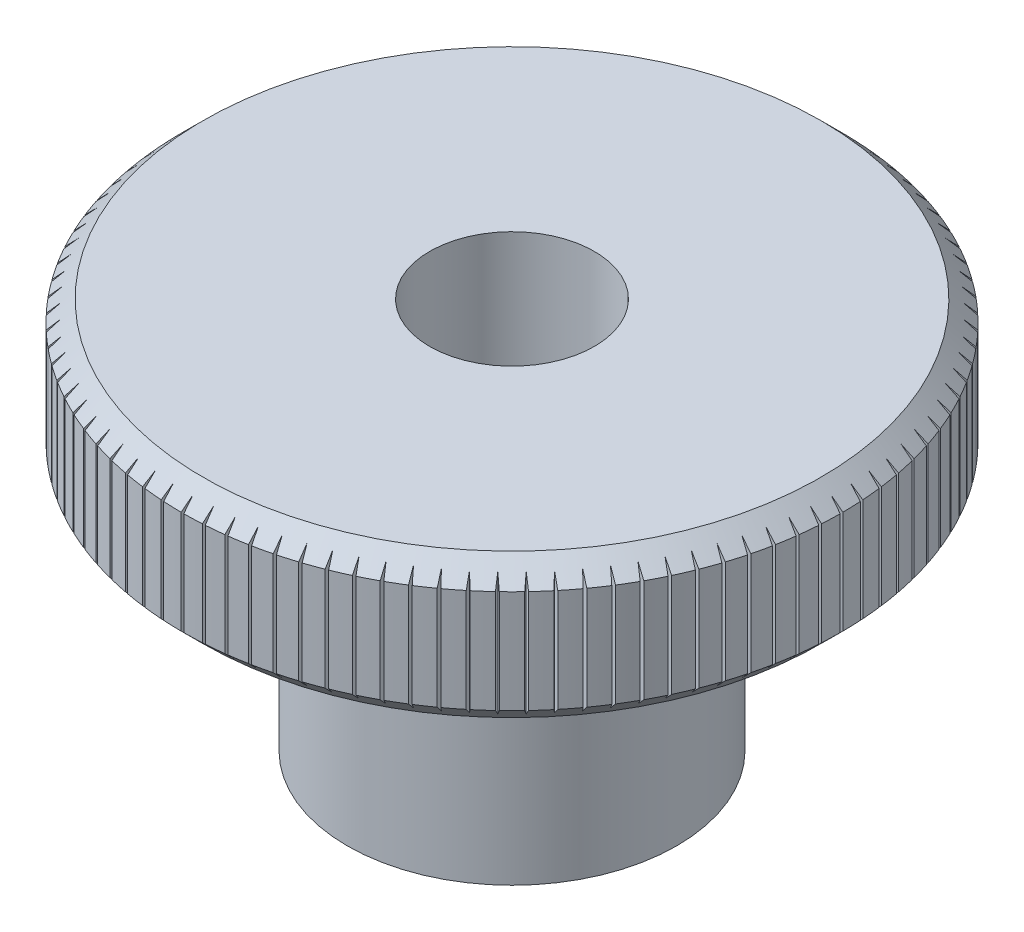
SolidWorks part; units mm, degrees
ref_plane "Front Plane" through (0, 0, 0) normal (0, 0, 1) x (1, 0, 0)
ref_plane "Top Plane" through (0, 0, 0) normal (0, 1, 0) x (1, 0, 0)
ref_plane "Right Plane" through (0, 0, 0) normal (1, 0, 0) x (0, 0, -1)
sketch "Sketch1" plane through (0, 0, 0) normal (0, 0, 1) x (1, 0, 0)
  line L0 (0, 0) -> (0, -3885.4477) construction
  line L1 (2, 0) -> (2, 9.5)
  line L2 (2, 9.5) -> (8, 9.5)
  line L3 (8, 9.5) -> (8, 6)
  line L4 (8, 6) -> (4, 6)
  line L5 (4, 6) -> (4, 0)
  line L6 (4, 0) -> (2, 0)
  dimension "INNER DIAM" = 4
  dimension "HEAD DIAM" = 16
  dimension "BOSS DIAM" = 8
  dimension "HEIGHT" = 9.5
  dimension "KNURLED HEIGHT" = 3.5
revolve "Revolve1" add sketch "Sketch1" angle 360 about L0
fillet "Fillet1" radius 0.8 1 edges at (0, 6, 4)
chamfer "Chamfer1" distance 0.5 angle 45 2 edges at (0, 6, 8) (0, 9.5, 8)
sketch "Sketch2" plane through (0, 9.5, 0) normal (0, 1, 0) x (1, 0, 0)
  line L0 (0.0329, 8) -> (-0.0329, 8)
  line L1 (-0.0329, 8) -> (0, 7.75)
  line L2 (0, 7.75) -> (0.0329, 8)
  circle A1 centre (0, 0) radius 8 construction
  point P0 (0, 8)
  point P3 (0, 8)
  dimension "D1" = 0.25
  dimension "D2" = 15
extrude "Cut-Extrude1" cut sketch "Sketch2" against normal through all
pattern_circular "CirPattern1" count 100 over 360 about axis through (0, 0, 0) along (0, 1, 0) of "Cut-Extrude1" reverse direction yes
equation "\"D1@Fillet1\"= \"INNER DIAM@Sketch1\" / 5"
equation "\"D1@Chamfer1\" = \"INNER DIAM@Sketch1\" / 8"
equation "\"D1@Sketch2\"= \"D1@Chamfer1\" / 2"
